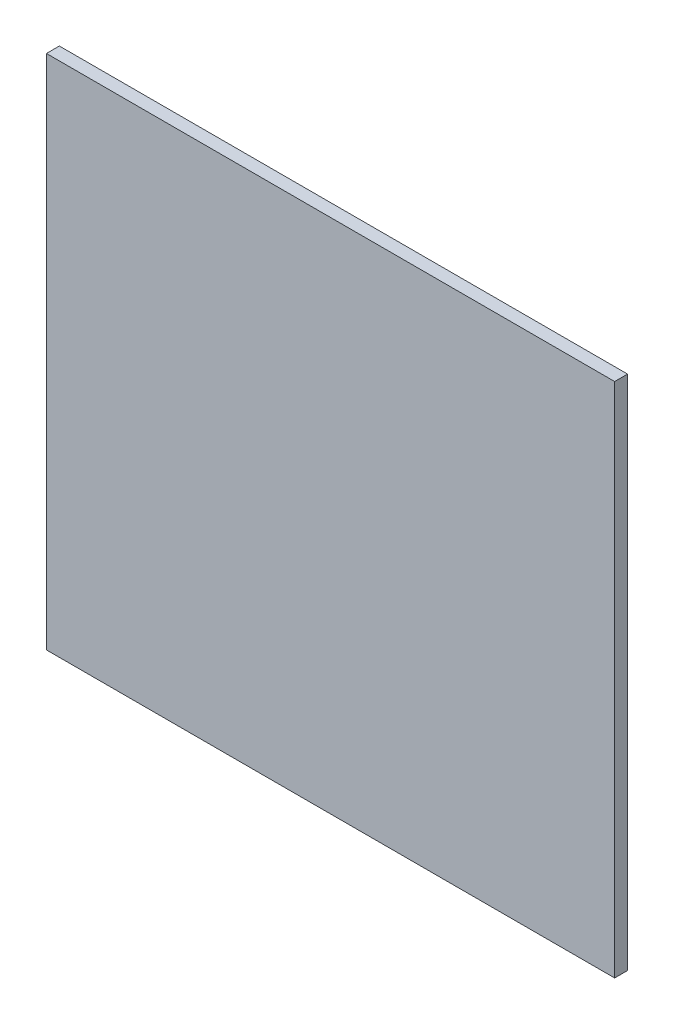
SolidWorks part; units mm, degrees
ref_plane "Front Plane" through (0, 0, 0) normal (0, 0, 1) x (1, 0, 0)
ref_plane "Top Plane" through (0, 0, 0) normal (0, 1, 0) x (1, 0, 0)
ref_plane "Right Plane" through (0, 0, 0) normal (1, 0, 0) x (0, 0, -1)
sketch "Sketch1" plane through (0, 0, 0) normal (0, 0, 1) x (1, 0, 0)
  line L1 (-69.85, 63.5) -> (69.85, 63.5)
  line L2 (-69.85, 63.5) -> (-69.85, -63.5)
  line L3 (-69.85, -63.5) -> (69.85, -63.5)
  line L4 (69.85, 63.5) -> (69.85, -63.5)
  line L5 (-69.85, 63.5) -> (69.85, -63.5) construction
  line L6 (-69.85, -63.5) -> (69.85, 63.5) construction
  line L10 (58.2701, -50.8698) -> (58.2701, 50.8698)
  line L11 (58.2701, 50.8698) -> (-58.2701, 50.8698)
  line L12 (-58.2701, 50.8698) -> (-58.2701, -50.8698)
  line L13 (-58.2701, -50.8698) -> (58.2701, -50.8698)
  line L14 (58.2701, -50.8698) -> (58.2701, 50.8698) construction
  line L15 (58.2701, 50.8698) -> (-58.2701, 50.8698)
  line L16 (-58.2701, 50.8698) -> (-58.2701, -50.8698)
  line L17 (-58.2701, -50.8698) -> (58.2701, -50.8698)
  point P0 (0, 0)
  dimension "D2" = 116.5403
  dimension "D3" = 101.7397
  dimension "D4" = 127
  dimension "D5" = 139.7
  dimension "D1" = 0
extrude "Boss-Extrude1" add sketch "Sketch1" along normal blind 3.175 contours L2 L1 L4 L3
